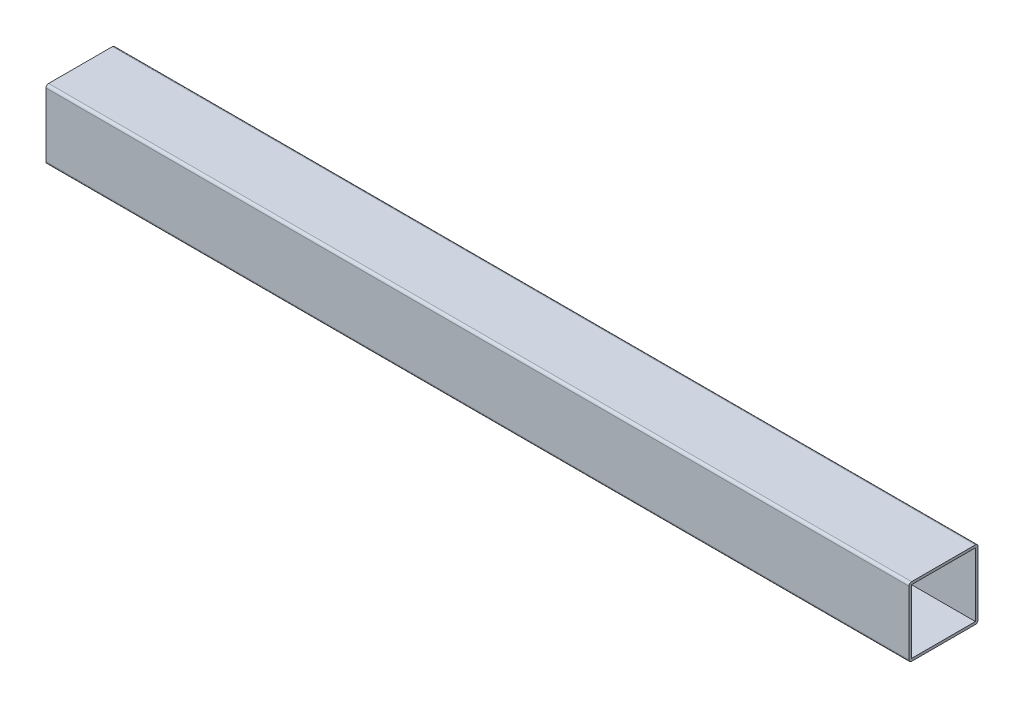
SolidWorks part; units mm, degrees
ref_plane "Спереди" through (0, 0, 0) normal (0, 0, 1) x (1, 0, 0)
ref_plane "Сверху" through (0, 0, 0) normal (0, 1, 0) x (1, 0, 0)
ref_plane "Справа" through (0, 0, 0) normal (1, 0, 0) x (0, 0, -1)
sketch "Эскиз1" plane through (0, 0, 0) normal (1, 0, 0) x (0, 0, -1)
  line L1 (3, 0) -> (77, 0)
  line L2 (0, 3) -> (0, 77)
  line L3 (3, 80) -> (77, 80)
  line L4 (80, 3) -> (80, 77)
  arc A0 (0, 3) -> (3, 0) centre (3, 3) ccw
  arc A1 (77, 0) -> (80, 3) centre (77, 3) ccw
  arc A2 (77, 80) -> (80, 77) centre (77, 77) cw
  arc A3 (0, 77) -> (3, 80) centre (3, 77) cw
  point P7 (0, 0)
  dimension "D1" = 3
extrude "Вытянуть-Тонкостенный1" add sketch "Эскиз1" along normal blind 1000 thin thin type one direction reverse wall 3
